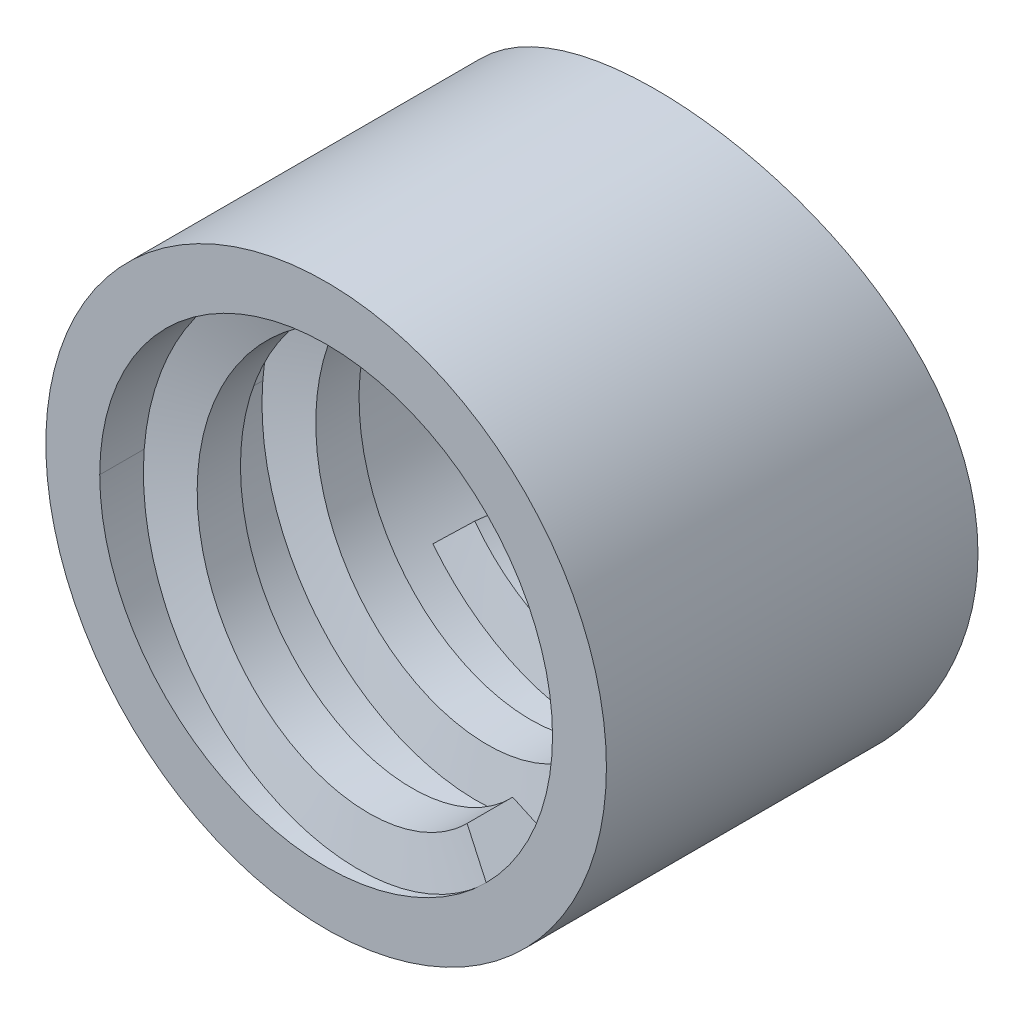
SolidWorks part; units mm, degrees
ref_plane "前视基准面" through (0, 0, 0) normal (0, 0, 1) x (1, 0, 0)
ref_plane "上视基准面" through (0, 0, 0) normal (0, 1, 0) x (1, 0, 0)
ref_plane "右视基准面" through (0, 0, 0) normal (1, 0, 0) x (0, 0, -1)
sketch "草图1" plane through (0, 0, 0) normal (0, 0, 1) x (1, 0, 0)
  circle A0 centre (0, 0) radius 13
extrude "凸台-拉伸1" add sketch "草图1" along normal blind 12.375 and the other way blind 13
sketch "草图2" plane through (0, 0, 0) normal (0, 0, 1) x (1, 0, 0)
  circle A0 centre (0, 0) radius 10.5
extrude "切除-拉伸1" cut sketch "草图2" against normal blind 10 and the other way blind 20
sketch "草图3" plane through (0, 0, 0) normal (0, 0, 1) x (1, 0, 0)
  circle A0 centre (0, 0) radius 10.5
curve "螺旋线/涡状线1" pitch 5.5 height 12.375 radius 10.5 centre (0, 0, 0) axis (0, 0, 1) start towards (1, 0, 0)
ref_plane "基准面1" through (-7.4246, -7.4246, 0) normal (0.7047, -0.7047, 0.0831) x (0.0587, -0.0587, -0.9965)
sketch "草图4" plane through (-7.4246, -7.4246, 0) normal (0.7047, -0.7047, 0.0831) x (0.0587, -0.0587, -0.9965)
  line L0 (0, 0) -> (3, 0)
  line L1 (0.5, 2) -> (2.5, 2)
  line L2 (2.5, 2) -> (3, 0)
  line L3 (0.5, 2) -> (0, 0)
  line L4 (0, 0) -> (-0.108, 0.0401)
sweep "扫描1" add profiles "草图4" path "螺旋线/涡状线1"
ref_plane "基准面2" through (0, 0, -3) normal (0, 0, 1) x (1, 0, 0)
sketch "草图5" plane through (0, 0, -3) normal (0, 0, 1) x (1, 0, 0)
  line L0 (-7.4589, 0) -> (7.8411, 0) construction
ref_plane "基准面3" through (0, 0, 0) normal (0, -1, 0) x (-1, 0, 0)
sketch "草图6" plane through (0, 0, 0) normal (0, -1, 0) x (-1, 0, 0)
  line L0 (-6.5836, 48) -> (8.0191, 48) construction
  line L1 (7.4589, 3) -> (-7.8411, 3) construction
  line L2 (-0.1911, 62.931) -> (-0.1911, 0) construction
  circle A0 centre (-0.1911, 48) radius 45.0028
  dimension "D1" = 45
extrude "切除-拉伸2" cut sketch "草图6" against normal blind 20 and the other way blind 20
